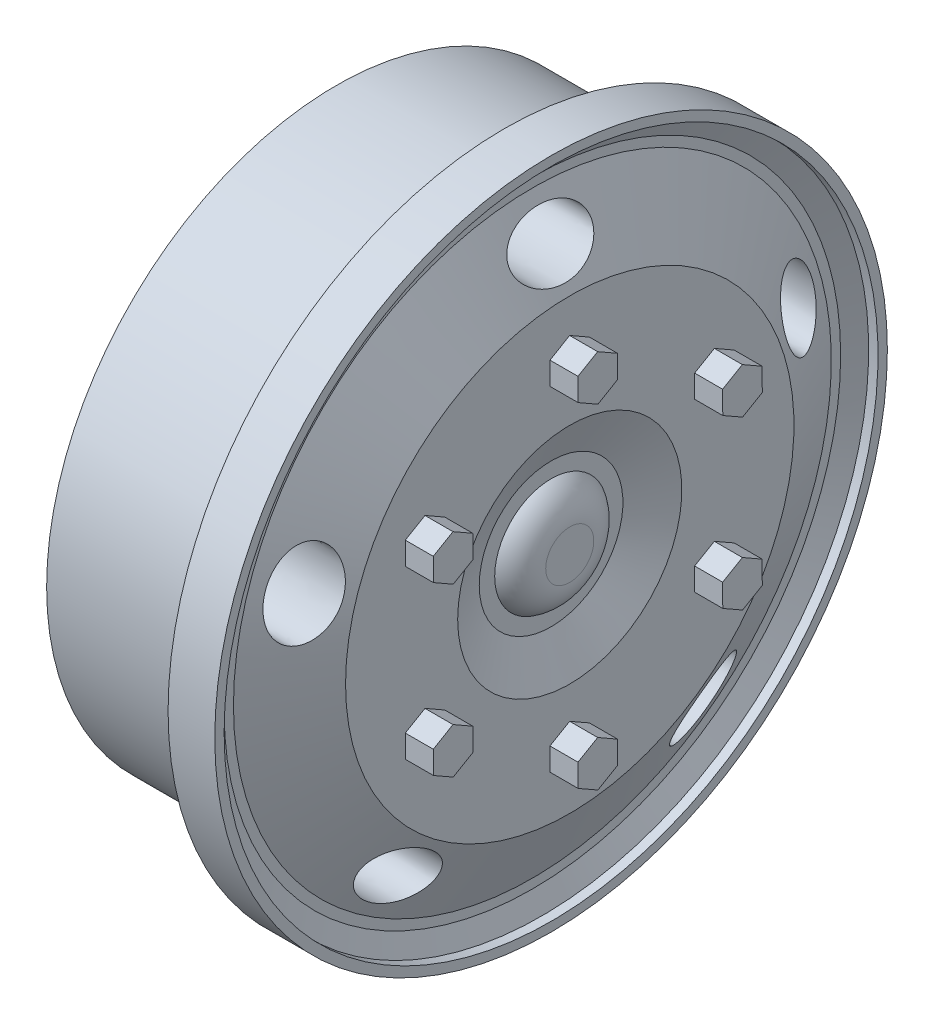
SolidWorks part; units mm, degrees
ref_plane "Front Plane" through (0, 0, 0) normal (0, 0, 1) x (1, 0, 0)
ref_plane "Top Plane" through (0, 0, 0) normal (0, 1, 0) x (1, 0, 0)
ref_plane "Right Plane" through (0, 0, 0) normal (1, 0, 0) x (0, 0, -1)
sketch "Sketch1" plane through (0, 0, 0) normal (0, 1, 0) x (1, 0, 0)
  line L0 (-25, 0) -> (25, 0) construction
  line L9 (5.5, 0) -> (-5.5, 0)
  line L11 (-5.5, 0) -> (-5.5, 15.5)
  line L12 (-5.5, 15.5) -> (3.5, 15.5)
  line L13 (3.5, 15.5) -> (3.5, 18)
  line L14 (3.5, 18) -> (5.5, 18)
  line L20 (5.5, 18) -> (6, 18)
  line L21 (6, 18) -> (6, 17.5)
  line L22 (6, 17.5) -> (5.5, 17.5)
  line L24 (5, 16.5) -> (5, 16)
  line L25 (5, 16) -> (7, 12)
  line L27 (5.5, 17.5) -> (5, 16.5)
  line L28 (7, 12) -> (7, 6)
  line L29 (7, 0) -> (5.5, 0)
  line L30 (7, 6) -> (6, 3.8452)
  line L31 (6, 3.8452) -> (6, 3.0185)
  line L32 (6, 3.0185) -> (7, 2.5545)
  line L33 (7, 2.5545) -> (7, 0)
  dimension "D1" = 50
  dimension "D2" = 25
  dimension "D3" = 11
  dimension "D4" = 5.5
  dimension "D5" = 36
  dimension "D6" = 2.5
  dimension "D7" = 0.5
  dimension "D8" = 0.5
  dimension "D9" = 1.5
  dimension "D10" = 2
  dimension "D11" = 4
  dimension "D12" = 2
revolve "Revolve1" add sketch "Sketch1" angle 360 about L0
sketch "Sketch3" plane through (7, 0, 0) normal (1, 0, 0) x (0, 0, -1)
  ellipse E0 centre (0, 13.9262) end of major axis (2.2166, 13.9262) minor radius 1.4456
  ellipse E1 centre (13.2446, 4.3034) end of major axis (12.5596, 6.4116) minor radius 1.4456
  ellipse E2 centre (8.1856, -11.2665) end of major axis (9.9789, -9.9636) minor radius 1.4456
  ellipse E3 centre (-8.1856, -11.2665) end of major axis (-6.3923, -12.5694) minor radius 1.4456
  ellipse E4 centre (-13.2446, 4.3034) end of major axis (-12.5596, 6.4116) minor radius 1.4456
  point P1 (0, 0)
  point P33 (0, 0)
  dimension "D1" = 5
extrude "Cut-Extrude1" cut sketch "Sketch3" against normal mid plane 10
fillet "Fillet1" radius 2 1 edges at (7, 0, 2.5545)
sketch "Sketch4" plane through (7, 0, 0) normal (1, 0, 0) x (0, 0, -1)
  line L0 (7.7496, 3.2501) -> (8.804, 3.8655)
  line L1 (1.0601, 8.3364) -> (1.0544, 9.5572)
  line L2 (1.0544, 9.5572) -> (-0.0057, 10.1627)
  line L3 (-0.0057, 10.1627) -> (-1.0601, 9.5473)
  line L4 (-1.0601, 9.5473) -> (-1.0544, 8.3265)
  line L5 (-1.0544, 8.3265) -> (0.0057, 7.7211)
  line L6 (0.0057, 7.7211) -> (1.0601, 8.3364)
  line L7 (8.804, 3.8655) -> (8.7983, 5.0863)
  line L8 (8.7983, 5.0863) -> (7.7381, 5.6917)
  line L9 (7.7381, 5.6917) -> (6.6838, 5.0764)
  line L10 (6.6838, 5.0764) -> (6.6895, 3.8556)
  line L11 (6.6895, 3.8556) -> (7.7496, 3.2501)
  line L12 (6.6895, -5.0863) -> (7.7496, -5.6917)
  line L13 (7.7496, -5.6917) -> (8.804, -5.0764)
  line L14 (8.804, -5.0764) -> (8.7983, -3.8556)
  line L15 (8.7983, -3.8556) -> (7.7381, -3.2501)
  line L16 (7.7381, -3.2501) -> (6.6838, -3.8655)
  line L17 (6.6838, -3.8655) -> (6.6895, -5.0863)
  line L18 (-1.0601, -8.3364) -> (-1.0544, -9.5572)
  line L19 (-1.0544, -9.5572) -> (0.0057, -10.1627)
  line L20 (0.0057, -10.1627) -> (1.0601, -9.5473)
  line L21 (1.0601, -9.5473) -> (1.0544, -8.3265)
  line L22 (1.0544, -8.3265) -> (-0.0057, -7.7211)
  line L23 (-0.0057, -7.7211) -> (-1.0601, -8.3364)
  line L24 (-7.7496, -3.2501) -> (-8.804, -3.8655)
  line L25 (-8.804, -3.8655) -> (-8.7983, -5.0863)
  line L26 (-8.7983, -5.0863) -> (-7.7381, -5.6917)
  line L27 (-7.7381, -5.6917) -> (-6.6838, -5.0764)
  line L28 (-6.6838, -5.0764) -> (-6.6895, -3.8556)
  line L29 (-6.6895, -3.8556) -> (-7.7496, -3.2501)
  line L30 (-6.6895, 5.0863) -> (-7.7496, 5.6917)
  line L31 (-7.7496, 5.6917) -> (-8.804, 5.0764)
  line L32 (-8.804, 5.0764) -> (-8.7983, 3.8556)
  line L33 (-8.7983, 3.8556) -> (-7.7381, 3.2501)
  line L34 (-7.7381, 3.2501) -> (-6.6838, 3.8655)
  line L35 (-6.6838, 3.8655) -> (-6.6895, 5.0863)
  circle A0 centre (0, 0) radius 8.9419 construction
  circle A1 centre (0, 8.9419) radius 1.0573 construction
  point P44 (0, 0)
  dimension "D1" = 6
extrude "Boss-Extrude1" add sketch "Sketch4" along normal blind 1.5
